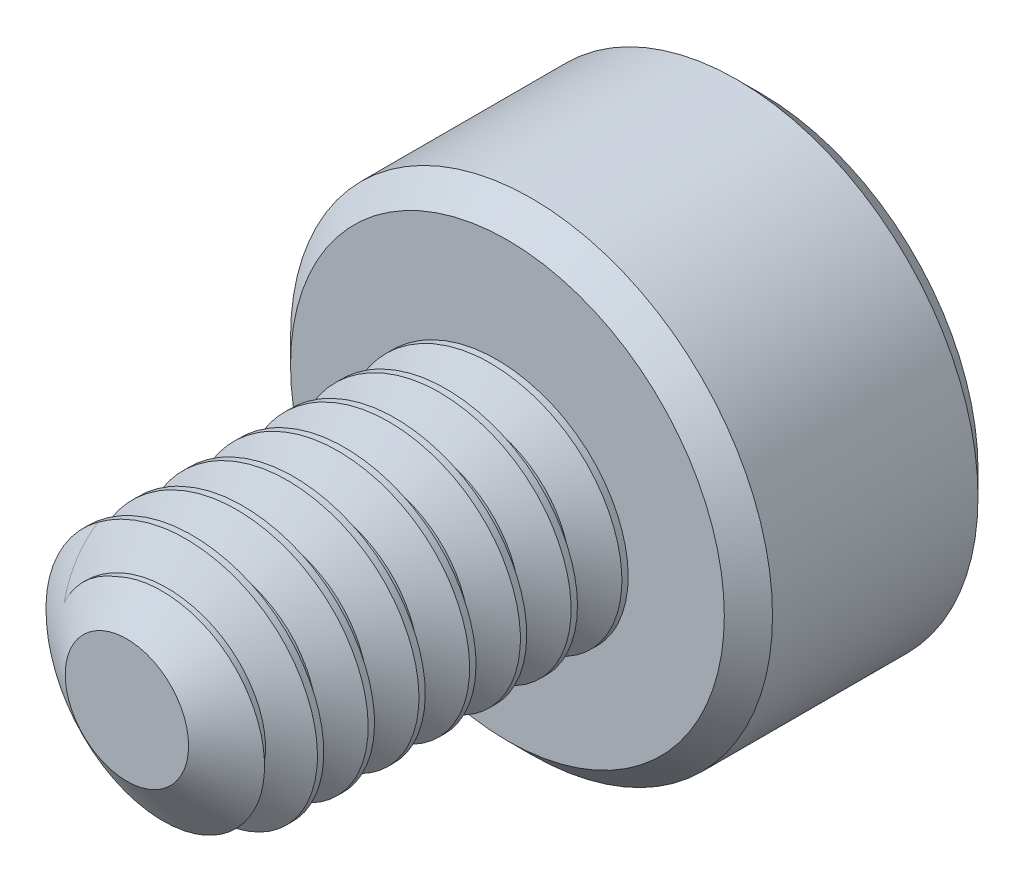
SolidWorks part; units mm, degrees
other "DetailItem1"
ref_plane "Front Plane" through (0, 0, 0) normal (0, 0, 1) x (1, 0, 0)
ref_plane "Top Plane" through (0, 0, 0) normal (0, 1, 0) x (1, 0, 0)
ref_plane "Right Plane" through (0, 0, 0) normal (1, 0, 0) x (0, 0, -1)
sketch "Sketch1" plane through (0, 0, 0) normal (0, 0, 1) x (1, 0, 0)
  circle A0 centre (0, 0) radius 1
  dimension "OD" = 2
extrude "Extrude1" add sketch "Sketch1" against normal blind 3
sketch "Sketch2" plane through (0, 0, 0) normal (0, 0, 1) x (1, 0, 0)
  circle A0 centre (0, 0) radius 1 construction
  circle A1 centre (0, 0) radius 1
curve "Helix/Spiral1" pitch 0.4 height 3.4 radius 1 centre (0, 0, 0) axis (0, 0, -1) start towards (0, 1, 0) parameters "pitch"=0.4
sketch "Sketch3" plane through (0, 0, 0) normal (1, 0, 0) x (0, 0, -1)
  line L0 (-0.35, 1) -> (-0.2, 0.7402)
  line L1 (-0.2, 0.7402) -> (-0.15, 0.7402)
  line L2 (-0.15, 0.7402) -> (0, 1)
  line L3 (-0.35, 1) -> (0, 1)
  line L4 (-0.175, 1) -> (-0.175, 0.7402) construction
  line L5 (-0.275, 0.8701) -> (-0.075, 0.8701) construction
  line L6 (0, 1) -> (0, -1) construction
  dimension "D1" = 0.05
  dimension "D2" = 0.2
  dimension "D3" = 60
sweep "Cut-Sweep1" cut profiles "Sketch3" path "Helix/Spiral1" align with end faces yes
sketch "Sketch4" plane through (0, 0, 0) normal (1, 0, 0) x (0, 0, -1)
  line L0 (0.3598, 1) -> (0, 0.4862)
  line L1 (0, 0.4862) -> (0, 1)
  line L2 (0.3598, 1) -> (0, 1)
  line L3 (-0.35, 1) -> (0, 1) construction
  line L4 (0, 0) -> (7.0209, 0) construction
  dimension "D1" = 55
  dimension "D2" = 0.254
revolve "Cut-Revolve1" cut sketch "Sketch4" angle 360 about L4
sketch "Sketch6" plane through (0, 0, -3) normal (0, 0, -1) x (-1, 0, 0)
  circle A0 centre (0, 0) radius 1.9
  dimension "head dia" = 3.8
extrude "Extrude2" add sketch "Sketch6" along normal blind 2
sketch "Sketch7" plane through (0, 0, -5) normal (0, 0, -1) x (-1, 0, 0)
  line L1 (0, 0.866) -> (-0.75, 0.433)
  line L2 (-0.75, 0.433) -> (-0.75, -0.433)
  line L3 (-0.75, -0.433) -> (0, -0.866)
  line L4 (0, -0.866) -> (0.75, -0.433)
  line L5 (0.75, -0.433) -> (0.75, 0.433)
  line L6 (0.75, 0.433) -> (0, 0.866)
  circle A0 centre (0, 0) radius 0.75 construction
  dimension "hex dia" = 1.5
extrude "Cut-Extrude1" cut sketch "Sketch7" against normal blind 1.125
sketch "Sketch8" plane through (0, 0, -5) normal (0, 0, -1) x (-1, 0, 0)
  circle A0 centre (0, 0) radius 0.866
extrude "Cut-Extrude2" cut sketch "Sketch8" against normal through all draft 45
chamfer "Chamfer1" distance 0.19 angle 45 2 edges at (-1.9, 0, -5) (-1.9, 0, -3)
sketch "Sketch10" plane through (0, 0, -3) normal (0, 0, 1) x (1, 0, 0)
  circle A1 centre (0, 0) radius 1
  circle A2 centre (0, 0) radius 1
  dimension "D1" = 0
ref_plane "Plane1" through (0, 0, 0) normal (0, 0, 1) x (1, 0, 0)
extrude "partial thread" [suppressed] add sketch "Sketch10" along normal up to surface (2 mm away) separate body up to plane "Plane1"
chamfer "Chamfer2" [suppressed] distance 0.04 angle 45
combine bodies "Combine1" [suppressed] operation type add bodies to combine 107 108
sketch "Sketch9" plane through (0, 0, 0) normal (1, 0, 0) x (0, 0, -1)
  line L0 (0, 1) -> (0, -1) construction
  line L1 (1, 1) -> (1, -1) construction
  dimension "D1" = 1
equation "\"D3@Helix/Spiral1\" = \"screw length@Extrude1\"+\"pitch@Helix/Spiral1\""
equation "\"D1@Sketch3\" = \"pitch@Helix/Spiral1\"*.125"
equation "\"D2@Sketch3\" = \"pitch@Helix/Spiral1\"*.5"
equation "\"D1@Cut-Extrude1\" = \"hex dia@Sketch7\"*.75"
equation "\"D1@Chamfer1\" = \"head dia@Sketch6\"*.05"
equation "\"D1@Sketch9\" = \"pitch@Helix/Spiral1\"*2.5"
equation "\"D1@Chamfer2\"=\"OD@Sketch1\"*.02"
